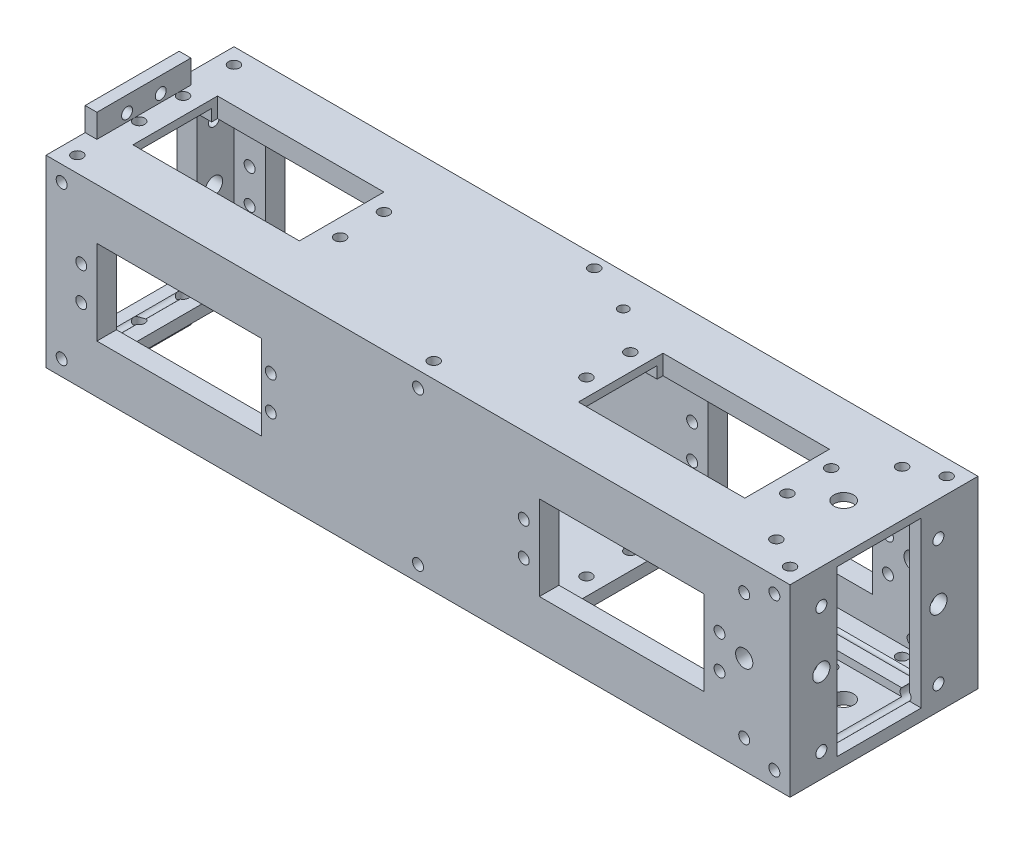
SolidWorks part; units mm, degrees
material "ABS"
ref_plane "Plano frontal" through (0, 0, 0) normal (0, 0, 1) x (1, 0, 0)
ref_plane "Plano superior" through (0, 0, 0) normal (0, 1, 0) x (1, 0, 0)
ref_plane "Plano direito" through (0, 0, 0) normal (1, 0, 0) x (0, 0, -1)
sketch "Esboço1" plane through (0, 0, 0) normal (0, 0, 1) x (1, 0, 0)
  line L1 (0, 0) -> (190, 0)
  line L2 (0, 0) -> (0, 47)
  line L3 (0, 47) -> (190, 47)
  line L4 (190, 0) -> (190, 47)
  dimension "D1" = 190
  dimension "D2" = 47
extrude "Ressalto-extrusão1" add sketch "Esboço1" along normal blind 46 and the other way blind 2
sketch "Esboço2" plane through (0, 0, 0) normal (1, 0, 0) x (0, 0, -1)
  line L1 (-41, 42) -> (-3, 42)
  line L2 (-41, 42) -> (-41, 5)
  line L3 (-41, 5) -> (-3, 5)
  line L4 (-3, 42) -> (-3, 5)
  dimension "D1" = 5
  dimension "D2" = 5
  dimension "D3" = 5
  dimension "D4" = 5
extrude "Corte-extrusão1" cut sketch "Esboço2" along normal through all
sketch "Esboço3" plane through (0, 0, 0) normal (0, 0, 1) x (1, 0, 0)
  line L1 (55, 34) -> (13, 34)
  line L2 (55, 34) -> (55, 12.4)
  line L3 (55, 12.4) -> (13, 12.4)
  line L4 (13, 34) -> (13, 12.4)
  circle A0 centre (205.6134, 31.5003) radius 1.25
  circle A1 centre (9, 27.5) radius 1.4
  circle A2 centre (9, 18.9) radius 1.4
  circle A3 centre (57.4, 27.5) radius 1.4
  circle A4 centre (57.4, 18.9) radius 1.4
  dimension "D6" = 2.8
  dimension "D1" = 13
  dimension "D2" = 21.6
  dimension "D3" = 13
  dimension "D4" = 42
  dimension "D7" = 2
  dimension "D8" = 6.5
  dimension "D10" = 6.5
  dimension "D11" = 4
  dimension "D12" = 4
  dimension "D13" = 2
extrude "Corte-extrusão6" cut sketch "Esboço3" along normal through all and the other way through all
sketch "Esboço8" plane through (0, 0, 0) normal (1, 0, 0) x (0, 0, -1)
  line L1 (2, 47) -> (-46, 47)
  line L2 (2, 47) -> (2, 0)
  line L3 (2, 0) -> (-46, 0)
  line L4 (-46, 47) -> (-46, 0)
sketch "Esboço11" plane through (0, 0, 0) normal (0, 0, 1) x (1, 0, 0)
  line L0 (0, 0) -> (190, 0) construction
  line L1 (190, 47) -> (187, 47)
  line L2 (190, 47) -> (190, 0)
  line L3 (190, 0) -> (187, 0)
  line L4 (187, 47) -> (187, 0)
  dimension "D1" = 3
extrude "Ressalto-extrusão4" add sketch "Esboço11" along normal through all
extrude "Ressalto-extrusão5" add sketch "Esboço8" along normal blind 5
sketch "Esboço12" plane through (0, 0, 0) normal (1, 0, 0) x (0, 0, -1)
  line L0 (-12.5, 45) -> (-34, 45)
  line L1 (-12.5, 45) -> (-12.5, 3)
  line L2 (-12.5, 3) -> (-34, 3)
  line L3 (-34, 45) -> (-34, 3)
  dimension "D1" = 21.5
  dimension "D2" = 42
  dimension "D3" = 12
  dimension "D4" = 3
extrude "Corte-extrusão8" cut sketch "Esboço12" along normal through all
sketch "Esboço13" plane through (0, 47, 0) normal (0, 1, 0) x (1, 0, 0)
  line L0 (190, 2) -> (190, -46) construction
  circle A0 centre (178.2104, -5.6) radius 1.4
  circle A1 centre (178.2104, -37.7) radius 1.4
  dimension "D1" = 2.8
  dimension "D2" = 11.7896
  dimension "D4" = 7.6
  dimension "D3" = 2
extrude "Corte-extrusão10" cut sketch "Esboço13" against normal through all
sketch "Esboço14" plane through (0, 47, 0) normal (0, 1, 0) x (1, 0, 0)
  circle A0 centre (178.2104, -20.5) radius 2.5
  circle A1 centre (178.2104, -5.6) radius 1.4 construction
  dimension "D1" = 14.9
  dimension "D2" = 5
  dimension "D3" = 0
extrude "Corte-extrusão12" cut sketch "Esboço14" against normal through all
sketch "Esboço16" plane through (0, 0, 0) normal (0, 0, 1) x (1, 0, 0)
  line L0 (190, 0) -> (190, 47) construction
  circle A0 centre (178.3, 39.4037) radius 1.4
  circle A1 centre (178.3, 7.3037) radius 1.4
  circle A2 centre (178.3, 24.9086) radius 2.2
  dimension "D4" = 4.4
  dimension "D1" = 11.7
  dimension "D2" = 11.7
  dimension "D3" = 32.1
extrude "Corte-extrusão14" cut sketch "Esboço16" against normal through all and the other way through all
sketch "Esboço17" plane through (190, 0, 0) normal (1, 0, 0) x (0, 0, -1)
  circle A0 centre (-38, 38.2451) radius 1.4
  circle A1 centre (-38, 6.1451) radius 1.4
  circle A2 centre (-38, 23.75) radius 2.2
  circle A3 centre (-8.1067, 38.2451) radius 1.4
  circle A4 centre (-8.1067, 23.75) radius 2.2
  circle A5 centre (-8.1067, 6.1451) radius 1.4
  dimension "D7" = 0
  dimension "D6" = 2
extrude "Corte-extrusão15" cut sketch "Esboço17" against normal through all and the other way blind 194
sketch "Esboço18" plane through (0, 0, 0) normal (0, 0, 1) x (1, 0, 0)
  line L1 (168, 34) -> (126, 34)
  line L2 (168, 34) -> (168, 12.4)
  line L3 (168, 12.4) -> (126, 12.4)
  line L4 (126, 34) -> (126, 12.4)
  line L5 (55, 34) -> (13, 34) construction
  circle A0 centre (319.9479, 27.2666) radius 1.25
  circle A1 centre (122, 27.5) radius 1.4
  circle A2 centre (122, 18.9) radius 1.4
  circle A3 centre (172, 27.5) radius 1.4
  circle A4 centre (172, 18.9) radius 1.4
  dimension "D3" = 2.8
  dimension "D1" = 42
  dimension "D2" = 21.6
  dimension "D4" = 6.5
  dimension "D5" = 6.5
  dimension "D6" = 4
  dimension "D7" = 4
  dimension "D8" = 0
  dimension "D9" = 0
  dimension "D10" = 0
  dimension "D11" = 4
  dimension "D12" = 4
  dimension "D13" = 71
extrude "Corte-extrusão16" cut sketch "Esboço18" against normal through all and the other way through all
sketch "Esboço5" plane through (0, 0, 0) normal (0, 1, 0) x (1, 0, 0)
  line L0 (51.3, -11) -> (8.8, -11)
  line L1 (51.3, -11) -> (51.3, -32.6)
  line L2 (51.3, -32.6) -> (8.8, -32.6)
  line L3 (8.8, -11) -> (8.8, -32.6)
  line L4 (-60.6423, 10.8) -> (-103.1423, 10.8)
  line L5 (-60.6423, 10.8) -> (-60.6423, -10.8)
  line L6 (-60.6423, -10.8) -> (-103.1423, -10.8)
  line L7 (-103.1423, 10.8) -> (-103.1423, -10.8)
  line L8 (0, -46) -> (0, 2) construction
  line L10 (165.058, -11) -> (122.558, -11)
  line L11 (165.058, -11) -> (165.058, -32.6)
  line L12 (165.058, -32.6) -> (122.558, -32.6)
  line L13 (122.558, -11) -> (122.558, -32.6)
  circle A0 centre (219.6346, -28.0756) radius 1.25
  circle A1 centre (4.4, -15.4) radius 1.4
  circle A2 centre (4.4, -26.6) radius 1.4
  circle A3 centre (55.7, -15.4) radius 1.4
  circle A4 centre (55.7, -26.6) radius 1.4
  circle A5 centre (107.6923, -6.2756) radius 1.25
  circle A6 centre (-107.5423, 6.4) radius 1.4
  circle A7 centre (-107.5423, -4.8) radius 1.4
  circle A8 centre (-56.2423, 6.4) radius 1.4
  circle A9 centre (-56.2423, -4.8) radius 1.4
  circle A10 centre (118.158, -14.9401) radius 1.4
  circle A11 centre (118.158, -26.1401) radius 1.4
  circle A12 centre (169.458, -14.9401) radius 1.4
  circle A13 centre (169.458, -26.1401) radius 1.4
  dimension "D1" = 4.4
  dimension "D2" = 4.4
  dimension "D3" = 4.4
  dimension "D4" = 13
  dimension "D5" = 4.4
  dimension "D6" = 21.6
  dimension "D7" = 4.4
  dimension "D8" = 21.6
  dimension "D9" = 4.4
  dimension "D10" = 0
  dimension "D11" = 11.2
  dimension "D13" = 4.4
  dimension "D14" = 0
  dimension "D15" = 42.5
  dimension "D16" = 0
  dimension "D17" = 11.2
  dimension "D18" = 0
  dimension "D19" = 4.4
  dimension "D20" = 0
  dimension "D21" = 42.5
extrude "Corte-extrusão4" cut sketch "Esboço5" along normal through all
sketch "Esboço19" plane through (0, 0, 0) normal (0, 1, 0) x (1, 0, 0)
  line L2 (190, -46) -> (0, -46) construction
  line L3 (0, 2) -> (190, 2) construction
  circle A0 centre (4, -2) radius 1.4
  circle A1 centre (4, -42) radius 1.4
  circle A2 centre (186, -2) radius 1.4
  circle A3 centre (186, -42) radius 1.4
  circle A4 centre (95, -42) radius 1.4
  circle A5 centre (95, -1) radius 1.4
  point P14 (95, -46)
  point P17 (95, -46)
  point P23 (95, 2)
  point P24 (95, 2)
  dimension "D1" = 4
  dimension "D2" = 4
  dimension "D3" = 4
  dimension "D4" = 4
  dimension "D5" = 4
  dimension "D6" = 4
  dimension "D7" = 4
  dimension "D8" = 4
  dimension "D9" = 0
  dimension "D10" = 4
  dimension "D11" = 0
  dimension "D12" = 3
extrude "Corte-extrusão17" cut sketch "Esboço19" against normal blind 74 and the other way through all
sketch "Esboço21" plane through (0, 0, 46) normal (0, 0, 1) x (1, 0, 0)
  line L0 (190, 47) -> (0, 47) construction
  line L1 (0, 0) -> (190, 0) construction
  circle A0 centre (4, 43) radius 1.4
  circle A1 centre (4, 4) radius 1.4
  circle A2 centre (186, 4) radius 1.4
  circle A3 centre (186, 43) radius 1.4
  circle A4 centre (95, 43) radius 1.4
  circle A5 centre (95, 4) radius 1.4
  point P15 (95, 47)
  point P18 (95, 47)
  point P21 (95, 0)
  point P24 (95, 0)
  dimension "D1" = 4
  dimension "D2" = 4
  dimension "D3" = 4
  dimension "D4" = 4
  dimension "D5" = 4
  dimension "D6" = 4
  dimension "D7" = 4
  dimension "D8" = 4
  dimension "D9" = 0
  dimension "D10" = 4
  dimension "D11" = 0
  dimension "D12" = 4
extrude "Corte-extrusão19" cut sketch "Esboço21" against normal blind 74 and the other way blind 74
sketch "Esboço22" plane through (0, 0, 0) normal (1, 0, 0) x (0, 0, -1)
  line L0 (2, 47) -> (-46, 47) construction
  line L1 (-36, 47) -> (-12, 47)
  line L2 (-36, 47) -> (-36, 53)
  line L3 (-36, 53) -> (-12, 53)
  line L4 (-12, 47) -> (-12, 53)
  line L5 (2, 0) -> (-46, 0) construction
  line L6 (-36, 0) -> (-12, 0)
  line L7 (-36, 0) -> (-36, -6)
  line L8 (-36, -6) -> (-12, -6)
  line L9 (-12, 0) -> (-12, -6)
  dimension "D1" = 24
  dimension "D2" = 6
  dimension "D3" = 6
  dimension "D4" = 24
  dimension "D5" = 10
  dimension "D6" = 10
extrude "Ressalto-extrusão6" add sketch "Esboço22" along normal blind 3
sketch "Esboço23" plane through (0, 0, 0) normal (1, 0, 0) x (0, 0, -1)
  circle A0 centre (-19.7, 49) radius 1.4
  circle A1 centre (-28.3, 49) radius 1.4
  circle A2 centre (-19.9, -1) radius 1.4
  circle A3 centre (-28.5, -1) radius 1.4
  dimension "D1" = 8.6
  dimension "D2" = 4
  dimension "D3" = 5.7
  dimension "D4" = 4
  dimension "D5" = 4
  dimension "D6" = 0
extrude "Corte-extrusão21" cut sketch "Esboço23" along normal blind 3
sketch "Esboço24" plane through (0, 0, 0) normal (0, 1, 0) x (1, 0, 0)
  line L0 (5.4, -42) -> (93.6, -42) construction
  circle A0 centre (95, -42) radius 1.4 construction
  text T0 "Robotinics rev 1.1 Maurinsoft.com"
extrude "Corte-extrusão22" cut sketch "Esboço24" along normal blind 2
